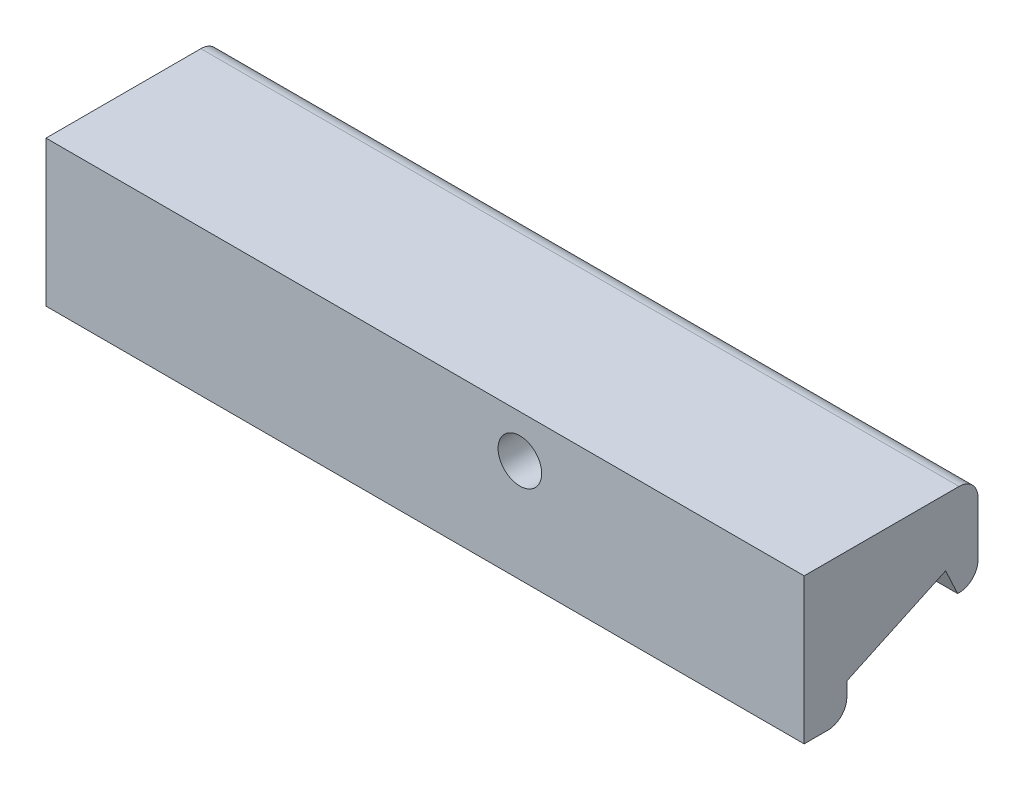
SolidWorks part; units mm, degrees
ref_plane "Front Plane" through (0, 0, 0) normal (0, 0, 1) x (1, 0, 0)
ref_plane "Top Plane" through (0, 0, 0) normal (0, 1, 0) x (1, 0, 0)
ref_plane "Right Plane" through (0, 0, 0) normal (1, 0, 0) x (0, 0, -1)
sketch "Sketch1" plane through (0, 0, 0) normal (1, 0, 0) x (0, 0, -1)
  line L0 (0, 0) -> (2.4995, 0)
  line L2 (18.3407, 7.6355) -> (18.3407, 13.3601)
  line L3 (16.3407, 15.3601) -> (0, 15.3601)
  line L4 (0, 15.3601) -> (0, 0)
  line L6 (16.1904, 5.6412) -> (14.9225, 8.3601)
  line L7 (14.9225, 8.3601) -> (4.5, 3.5)
  line L8 (4.5, 3.5) -> (4.5, 2.0005)
  arc A0 (16.3407, 15.3601) -> (18.3407, 13.3601) centre (16.3407, 13.3601) cw
  arc A1 (16.1904, 5.6412) -> (18.3407, 7.6355) centre (16.3407, 7.6355) ccw
  arc A2 (2.4995, 0) -> (4.5, 2.0005) centre (2.4995, 2.0005) ccw
  dimension "D7" = 4
  dimension "D8" = 4.0011
  dimension "D3" = 11.5
  dimension "D1" = 4.5
  dimension "D5" = 7
  dimension "D6" = 3
extrude "ProfileBoss-Extrude1" add sketch "Sketch1" along normal blind 80
sketch "Sketch2" plane through (0, 1.1513, 0.5368) normal (0, -0.9063, -0.4226) x (1, 0, 0)
  line L2 (80, -5.5575) -> (0, -5.5575) construction
  line L3 (0, -5.5575) -> (0, -17.0575) construction
  circle A0 centre (36.15, -11.3075) radius 2.3
  dimension "D1" = 4.6
  dimension "D2" = 5.75
  dimension "D3" = 36.15
extrude "LedStripMountHolesCut-Extrude1" cut sketch "Sketch2" against normal blind 4.5
sketch "Sketch4" plane through (0, 1.1513, 0.5368) normal (0, -0.9063, -0.4226) x (1, 0, 0)
  line L5 (80, -17.0575) -> (0, -17.0575) construction
  line L6 (0, -5.5575) -> (28, -5.5575)
  line L7 (0, -5.5575) -> (0, -17.0575)
  line L8 (0, -17.0575) -> (28, -17.0575)
  line L9 (28, -5.5575) -> (28, -17.0575)
  dimension "D2" = 28
extrude "PowerConnectorCut-Extrude4" cut sketch "Sketch4" against normal blind 6.5
sketch "Sketch3" plane through (0, 0, 0) normal (0, 0, 1) x (1, 0, 0)
  line L0 (0, 15.3601) -> (0, 0) construction
  circle A0 centre (50, 10.8601) radius 2.3
  dimension "D1" = 4.6
  dimension "D4" = 4.5
  dimension "D2" = 50
extrude "MountingHolesCut-Extrude3" cut sketch "Sketch3" against normal blind 4.5
equation "\"LightStripShortLength\"= 80mm"
equation "\"D1@ProfileBoss-Extrude1\"=\"LightStripShortLength\""
equation "\"LightStripWidth\"= 11.5mm'Spec"
equation "\"D3@Sketch1\"=\"LightStripWidth\""
equation "\"D2@Sketch2\"=\"LightStripWidth\"/2"
equation "\"LightStripMountHoleFromLeftOrRightEdge\"= ( \"LightStripLength\" - \"LightStripDistanceBetweenMountingHoles\" ) / 2"
equation "\"D3@Sketch2\"=\"LightStripMountHoleFromLeftOrRightEdge\""
equation "\"LightStripGuideMountingHoleFromLeftOrRightSide\"= 50mm"
equation "\"D2@Sketch3\"=\"LightStripGuideMountingHoleFromLeftOrRightSide\""
equation "\"LightStripGuideMountingHoleFromTop\"= 4.5mm"
equation "\"LightStripLength\"= 270mm'From Step file"
equation "\"LightStripDistanceBetweenMountingHoles\"= 197.7mm'From Step file"
